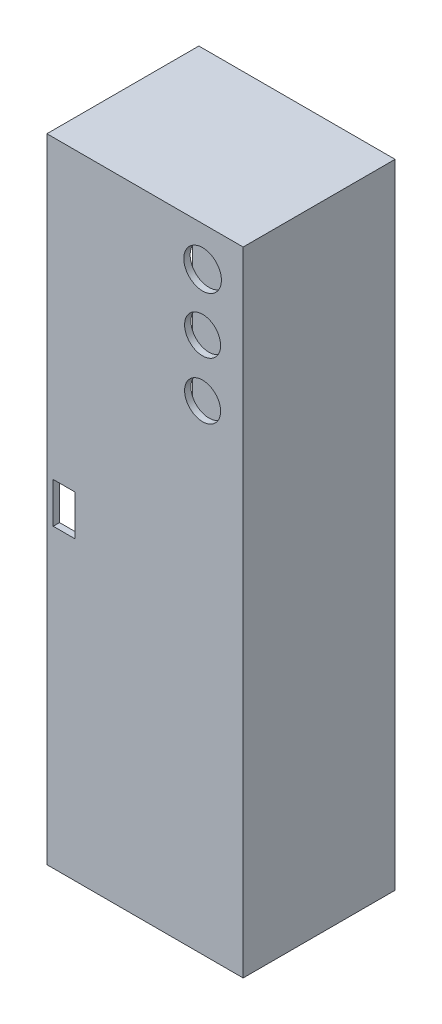
SolidWorks part; units mm, degrees
material "PLA"
ref_plane "Front Plane" through (0, 0, 0) normal (1, 0, 0) x (0, 1, 0)
ref_plane "Top Plane" through (0, 0, 0) normal (0, 0, 1) x (0, 1, 0)
ref_plane "Right Plane" through (0, 0, 0) normal (0, 1, 0) x (-1, 0, 0)
sketch "Sketch1" plane through (0, 0, 0) normal (0, 0, 1) x (0, 1, 0)
  line L1 (-125, -40) -> (125, -40)
  line L2 (-125, -40) -> (-125, 40)
  line L3 (-125, 40) -> (125, 40)
  line L4 (125, -40) -> (125, 40)
  line L5 (-125, -40) -> (125, 40) construction
  line L6 (-125, 40) -> (125, -40) construction
  point P0 (0, 0)
  dimension "D1" = 250
extrude "Boss-Extrude1" add sketch "Sketch1" along normal blind 2.5
sketch "Sketch2" plane through (0, 0, 0) normal (0, 0, -1) x (1, 0, 0)
  line L1 (-40, 125) -> (40, 125) construction
  line L2 (-37.5, -122.5) -> (37.5, -122.5)
  line L3 (-37.5, -122.5) -> (-37.5, 122.5)
  line L4 (-40, -125) -> (40, -125)
  line L5 (40, -125) -> (40, 125)
  line L6 (40, 125) -> (-40, 125)
  line L7 (-40, 125) -> (-40, -125)
  line L8 (-40, -125) -> (40, -125)
  line L9 (40, -125) -> (40, 125)
  line L10 (40, 125) -> (-40, 125)
  line L11 (-40, 125) -> (-40, -125)
  line L12 (-37.5, 122.5) -> (37.5, 122.5)
  line L13 (37.5, -122.5) -> (37.5, 122.5)
  line L14 (-37.5, -122.5) -> (37.5, 122.5) construction
  line L15 (-37.5, 122.5) -> (37.5, -122.5) construction
  point P2 (0, 0)
  dimension "D2" = 2.5
  dimension "D3" = 2.5
extrude "Boss-Extrude2" add sketch "Sketch2" along normal blind 55
sketch "Sketch3" plane through (0, 0, -55) normal (0, 0, -1) x (1, 0, 0)
  line L1 (40, 125) -> (-40, 125)
  line L2 (40, 125) -> (40, -125)
  line L3 (40, -125) -> (-40, -125)
  line L4 (-40, 125) -> (-40, -125)
extrude "Boss-Extrude3" add sketch "Sketch3" along normal blind 2.5
sketch "Sketch4" plane through (-40, 0, 0) normal (-1, 0, 0) x (0, -1, 0)
  line L5 (-125, 2.5) -> (125, 2.5)
  line L6 (-125, 2.5) -> (-125, -57.5)
  line L7 (-125, -57.5) -> (125, -57.5)
  line L8 (125, 2.5) -> (125, -57.5)
extrude "Cut-Extrude1" cut sketch "Sketch4" against normal blind 2.5
sketch "Sketch5" plane through (0, 0, 2.5) normal (0, 0, 1) x (1, 0, 0)
  line L0 (-26.5, 0) -> (-35, 0) construction
  line L1 (-35, 8) -> (-26.5, 8)
  line L2 (-35, 8) -> (-35, -8)
  line L3 (-35, -8) -> (-26.5, -8)
  line L4 (-26.5, 8) -> (-26.5, -8)
  line L6 (0, 0) -> (-37.5, 0) construction
  line L7 (-37.5, -125) -> (-37.5, 125) construction
  dimension "D3" = 2.5
  dimension "D1" = 16
  dimension "D2" = 8.5
extrude "Cut-Extrude2" cut sketch "Sketch5" against normal up to next
sketch "Sketch7" plane through (0, 0, -55) normal (0, 0, 1) x (1, 0, 0)
  line L0 (24.35, 17.1) -> (-5.65, 17.1) construction
  line L1 (-5.65, 12.9) -> (24.35, 12.9) construction
  line L2 (24.35, 17.1) -> (-5.65, 17.1) construction
  line L3 (-5.65, 12.9) -> (24.35, 12.9) construction
  line L4 (-37.5, -122.5) -> (37.5, -122.5)
  line L5 (37.5, -122.5) -> (37.5, 122.5)
  line L6 (37.5, 122.5) -> (-37.5, 122.5)
  line L7 (-37.5, 122.5) -> (-37.5, -122.5)
  line L8 (-37.5, -122.5) -> (37.5, -122.5)
  line L9 (37.5, -122.5) -> (37.5, 122.5)
  line L10 (37.5, 122.5) -> (-37.5, 122.5)
  line L11 (-37.5, 122.5) -> (-37.5, -122.5)
  line L12 (26.45, 15) -> (-7.75, 15) construction
  arc A0 (24.35, 12.9) -> (26.45, 15) centre (24.35, 15) ccw construction
  arc A1 (24.35, 12.9) -> (26.45, 15) centre (24.35, 15) ccw construction
  arc A2 (26.45, 15) -> (24.35, 17.1) centre (24.35, 15) ccw construction
  arc A3 (-7.75, 15) -> (-5.65, 12.9) centre (-5.65, 15) ccw construction
  arc A4 (-5.65, 17.1) -> (-7.75, 15) centre (-5.65, 15) ccw construction
  arc A5 (26.45, 15) -> (24.35, 17.1) centre (24.35, 15) ccw construction
  arc A6 (-7.75, 15) -> (-5.65, 12.9) centre (-5.65, 15) ccw construction
  arc A7 (-5.65, 17.1) -> (-7.75, 15) centre (-5.65, 15) ccw construction
  point P12 (21.45, 15)
  point P13 (-2.75, 15)
  dimension "D2" = 5
  dimension "D3" = 5
  dimension "D1" = 0
hole_wizard "M4 Clearance Hole1" positions "Sketch7" profile "Sketch11" hole size "M4" standard "ANSI Metric" end condition through all
sketch "Sketch11" plane through (-2.75, 15, -55) normal (1, 0, 0) x (0, -1, 0)
  line L0 (0, 0) -> (0, 2.5)
  line L1 (0, 2.5) -> (2.25, 2.5)
  line L2 (2.25, 2.5) -> (2.25, 0)
  line L5 (2.25, 0) -> (0, 0)
  line L11 (0, -6.35) -> (0, 107.95) construction
  dimension "Thru Hole Dia." = 4.5
  dimension "Thru Hole Depth" = 2.5
mirror "Mirror1" about plane through (0, 0, 0) normal (0, 1, 0) of "M4 Clearance Hole1"
sketch "Sketch13" plane through (0, 0, 2.5) normal (0, 0, 1) x (1, 0, 0)
  line L4 (40, 125) -> (-37.5, 125)
  line L5 (-37.5, 125) -> (-37.5, -125)
  line L6 (-37.5, -125) -> (40, -125)
  line L7 (40, -125) -> (40, 125)
  line L8 (40, 125) -> (-37.5, 125)
  line L9 (-37.5, 125) -> (-37.5, -125)
  line L10 (-37.5, -125) -> (40, -125)
  line L11 (40, -125) -> (40, 125)
  circle A0 centre (23.9838, 64.3649) radius 7.115 construction
  circle A1 centre (23.9838, 86.8649) radius 7.115 construction
  circle A2 centre (23.9838, 109.3649) radius 7.42 construction
  circle A3 centre (23.9838, 64.3649) radius 7.115
  circle A4 centre (23.9838, 86.8649) radius 7.115
  circle A5 centre (23.9838, 109.3649) radius 7.42
  dimension "D1" = 0
extrude "Cut-Extrude7" cut sketch "Sketch13" against normal up to surface (2.5 mm away) contours A5 | A4 | A3 up to face at (-30.75, 0, 0)
sketch "Sketch14" plane through (0, -125, 0) normal (0, -1, 0) x (1, 0, 0)
  circle A0 centre (26.722, -43.1326) radius 7.42 construction
  circle A1 centre (26.722, -43.1326) radius 7.42
extrude "Cut-Extrude8" cut sketch "Sketch14" against normal up to surface (2.5 mm away) up to face at (0, -122.5, -27.5)
equation "\"ball_diameter\"= 0.75in"
equation "\"wall_thickness\" = 0.25cm"
equation "\"track_length\" = 25cm"
equation "\"axle\" = 5mm"
equation "\"D1@Sketch1\"=\"track_length\""
equation "\"D1@Boss-Extrude1\"=\"wall_thickness\""
equation "\"D2@Sketch2\"=\"wall_thickness\""
equation "\"D3@Sketch2\"=\"wall_thickness\""
equation "\"D1@Boss-Extrude3\"=\"wall_thickness\""
equation "\"D3@Sketch5\"=\"wall_thickness\""
